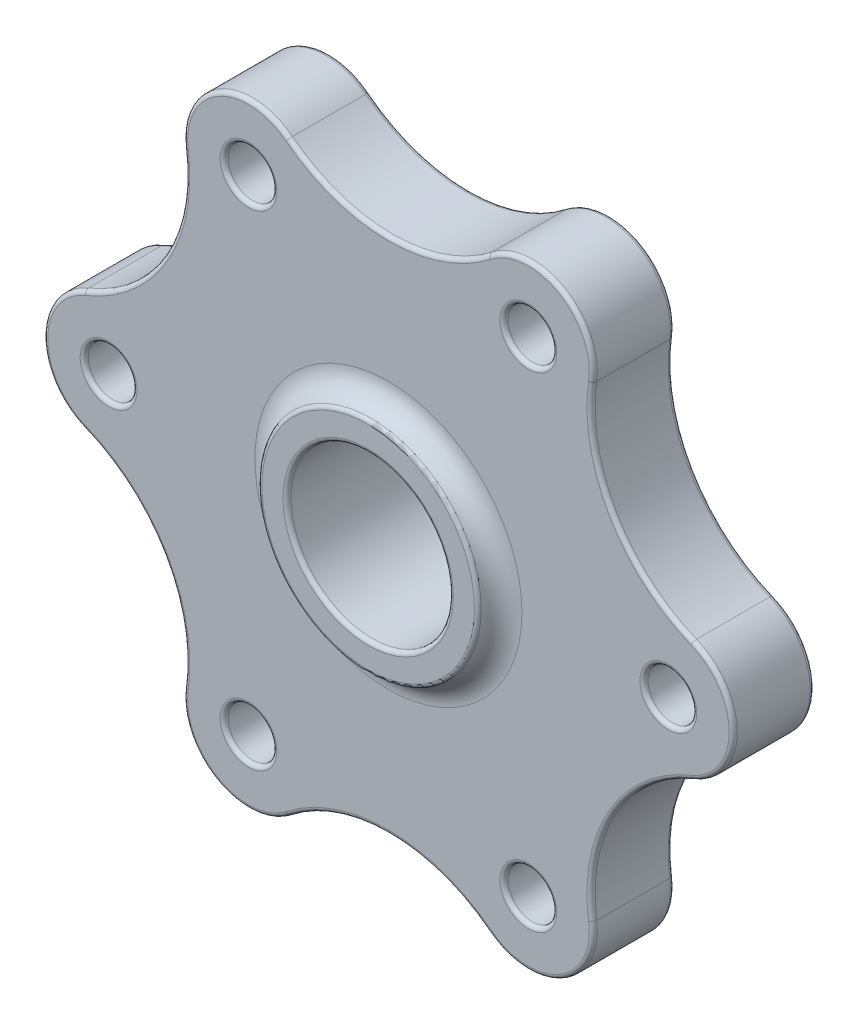
SolidWorks part; units mm, degrees
ref_plane "Front Plane" through (0, 0, 0) normal (0, 0, 1) x (1, 0, 0)
ref_plane "Top Plane" through (0, 0, 0) normal (0, 1, 0) x (1, 0, 0)
ref_plane "Right Plane" through (0, 0, 0) normal (1, 0, 0) x (0, 0, -1)
sketch "Sketch1" plane through (0, 0, 0) normal (0, 0, 1) x (1, 0, 0)
  line L0 (0, 0) -> (0, 30158.323) construction
  line L1 (0, 0) -> (30158.323, 0) construction
  circle A0 centre (0, 0) radius 10
  circle A1 centre (0, 0) radius 34.5 construction
  circle A2 centre (34.5, 0) radius 3
  arc A3 (37.493, -7.419) -> (37.493, 7.419) centre (34.5, 0) ccw
  circle A4 centre (17.25, -29.8779) radius 3
  arc A5 (12.3214, -36.1794) -> (25.1716, -28.7604) centre (17.25, -29.8779) ccw
  circle A6 centre (-17.25, -29.8779) radius 3
  arc A7 (-25.1716, -28.7604) -> (-12.3214, -36.1794) centre (-17.25, -29.8779) ccw
  circle A8 centre (-34.5, 0) radius 3
  arc A9 (-37.493, 7.419) -> (-37.493, -7.419) centre (-34.5, 0) ccw
  circle A10 centre (-17.25, 29.8779) radius 3
  arc A11 (-12.3214, 36.1794) -> (-25.1716, 28.7604) centre (-17.25, 29.8779) ccw
  circle A12 centre (17.25, 29.8779) radius 3
  arc A13 (25.1716, 28.7604) -> (12.3214, 36.1794) centre (17.25, 29.8779) ccw
  arc A14 (25.1716, 28.7604) -> (37.493, 7.419) centre (44.9755, 25.9666) ccw
  arc A15 (37.493, -7.419) -> (25.1716, -28.7604) centre (44.9755, -25.9666) ccw
  arc A16 (12.3214, -36.1794) -> (-12.3214, -36.1794) centre (0, -51.9332) ccw
  arc A17 (-25.1716, -28.7604) -> (-37.493, -7.419) centre (-44.9755, -25.9666) ccw
  arc A18 (-37.493, 7.419) -> (-25.1716, 28.7604) centre (-44.9755, 25.9666) ccw
  arc A19 (-12.3214, 36.1794) -> (12.3214, 36.1794) centre (0, 51.9332) ccw
  circle A20 centre (0, 0) radius 13.5
  point P29 (0, 0)
  point P48 (0, 0)
  dimension "D1" = 20
  dimension "D2" = 69
  dimension "D3" = 6
  dimension "D4" = 16
  dimension "D6" = 20
  dimension "D8" = 27
  dimension "D5" = 6
  dimension "D7" = 6
extrude "Boss-Extrude1" add sketch "Sketch1" along normal mid plane 15 contours A20 A0 region at (-13.1182, 0, 0)
extrude "Boss-Extrude2" add sketch "Sketch1<7>" along normal mid plane 10 contours A19 A11 A18 A9 A17 A7 A16 A5 A15 A3 A14 A13 A20 A12 A10 A8 A6 A4 A2 region at (26.6689, -15.3973, 0)
sketch "Sketch1<7>" plane through (0, 0, 0) normal (0, 0, 1) x (1, 0, 0) same geometry as "Sketch1"
fillet "Fillet1" radius 3 1 edges at (13.5, 0, 5)
fillet "Fillet2" radius 0.5 41 edges at (0, -31.9332, -5) (-21.25, -36.8061, -5) (-27.655, -15.9666, -5) (21.25, -36.8061, 5) (0, 31.9332, -5) (-21.25, 36.8061, -5) (-27.655, 15.9666, -5) (-42.5, 0, -5) (21.25, -36.8061, -5) (27.655, -15.9666, -5) (42.5, 0, -5) (27.655, 15.9666, -5) (21.25, 36.8061, -5) (20.25, 29.8779, -5) (-14.25, 29.8779, -5) (-31.5, 0, -5) (-14.25, -29.8779, -5) (20.25, -29.8779, -5) (37.5, 0, -5) (0, 31.9332, 5) (-21.25, 36.8061, 5) (-27.655, 15.9666, 5) (-42.5, 0, 5) (-27.655, -15.9666, 5) (-21.25, -36.8061, 5) (0, -31.9332, 5) (27.655, -15.9666, 5) (42.5, 0, 5) (27.655, 15.9666, 5) (21.25, 36.8061, 5) (20.25, 29.8779, 5) (-14.25, 29.8779, 5) (-31.5, 0, 5) (-14.25, -29.8779, 5) (20.25, -29.8779, 5) (37.5, 0, 5) (10, 0, -7.5) (13.5, 0, -7.5) (10, 0, 7.5) (13.5, 0, 7.5) (13.5, 0, -5)
